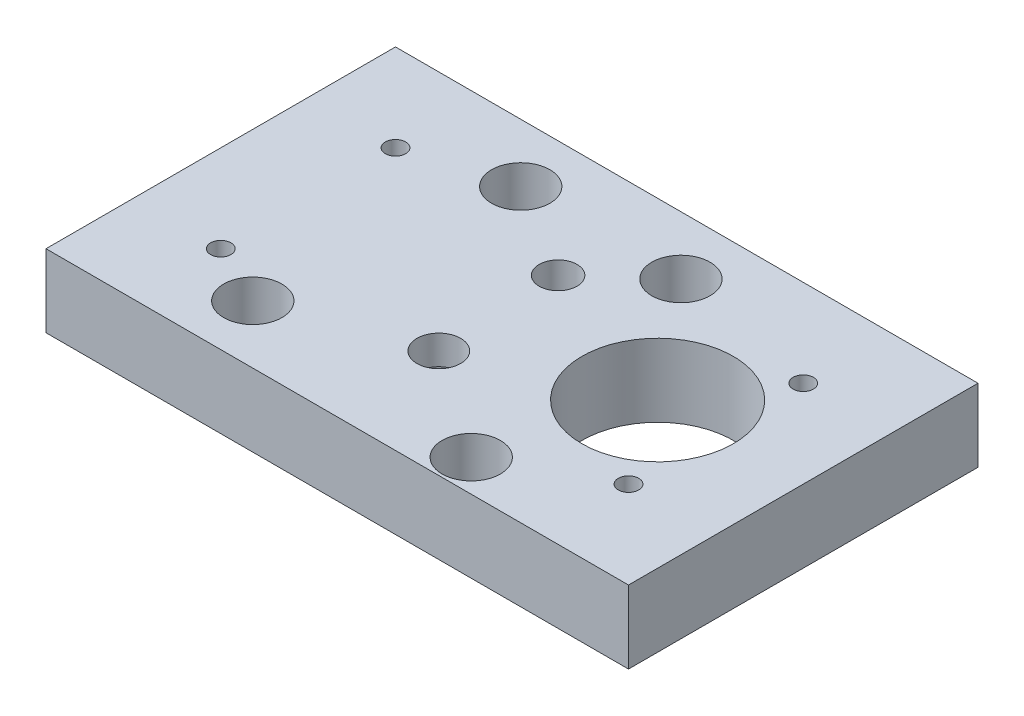
SolidWorks part; units mm, degrees
ref_plane "前视基准面" through (0, 0, 0) normal (0, 0, 1) x (1, 0, 0)
ref_plane "上视基准面" through (0, 0, 0) normal (0, 1, 0) x (1, 0, 0)
ref_plane "右视基准面" through (0, 0, 0) normal (1, 0, 0) x (0, 0, -1)
other "Configuration Table"
sketch "草图1" plane through (0, 0, 0) normal (0, 1, 0) x (1, 0, 0)
  line L0 (5.0509, -6) -> (27.896, -6) construction
  line L1 (0, 0) -> (20, 0)
  line L2 (0, 0) -> (0, -12)
  line L3 (0, -12) -> (20, -12)
  line L4 (20, 0) -> (20, -12)
  circle A2 centre (9.5826, -4) radius 0.65
  circle A3 centre (9.7826, -8.2953) radius 1.6
  circle A5 centre (15, -6) radius 2.6
  circle A6 centre (9.7826, -8.2953) radius 0.75
  point P5 (5, -6)
  dimension "D4" = 1.3
  dimension "D6" = 3.2
  dimension "D8" = 5.7
  dimension "D11" = 5.2
  dimension "D13" = 1.5
  dimension "D1" = 6
  dimension "D2" = 5
  dimension "D3" = 5
  dimension "D5" = 10
  dimension "D7" = 20
  dimension "D9" = 4.3
  dimension "D10" = 4
  dimension "D12" = 12
extrude "凸台-拉伸1" add sketch "草图1" along normal blind 2.5 contours L4 L3 L2 L1 | A2 | A3 | A5
extrude "凸台-拉伸2" add sketch "草图1<5>" against normal blind 1 from surface contours A3 | A6 starting at face at (10, 2.5, 6)
sketch "草图1<5>" plane through (0, 0, 0) normal (0, 1, 0) x (1, 0, 0) same geometry as "草图1"
sketch "草图3" plane through (0, 2.5, 0) normal (0, 1, 0) x (1, 0, 0)
  line L0 (0, 0) -> (0, -12) construction
  line L1 (0, 0) -> (20, 0) construction
  line L2 (0, -12) -> (20, -12) construction
  line L3 (20, 0) -> (20, -12) construction
  circle A0 centre (6.3, -2) radius 1
  circle A1 centre (5.1, -10) radius 1
  circle A2 centre (11.8, -2) radius 1
  circle A3 centre (13.5, -10.9) radius 1
  circle A4 centre (5.1, -10) radius 0.7
  circle A5 centre (6.3, -2) radius 0.7
  circle A6 centre (11.8, -2) radius 0.7
  circle A7 centre (13.5, -10.9) radius 0.7
  circle A11 centre (3, -3) radius 0.35
  circle A12 centre (3, -9) radius 0.35
  circle A13 centre (17, -9) radius 0.35
  circle A14 centre (17, -3) radius 0.35
  point P24 (2.9165, -4.193)
  dimension "D1" = 1.4
  dimension "D2" = 2
  dimension "D3" = 0.7
  dimension "D4" = 3
  dimension "D5" = 3
  dimension "D6" = 3
  dimension "D7" = 3
  dimension "D8" = 3
  dimension "D9" = 3
  dimension "D10" = 3
  dimension "D11" = 3
extrude "切除-拉伸1" cut sketch "草图3" against normal through all contours A5 | A4 | A6 | A7 | A12 | A11 | A14 | A13
extrude "切除-拉伸2" cut sketch "草图3<3>" against normal blind 1.5 contours A0 | A1 | A3 | A2
sketch "草图3<3>" plane through (0, 2.5, 0) normal (0, 1, 0) x (1, 0, 0) same geometry as "草图3"
